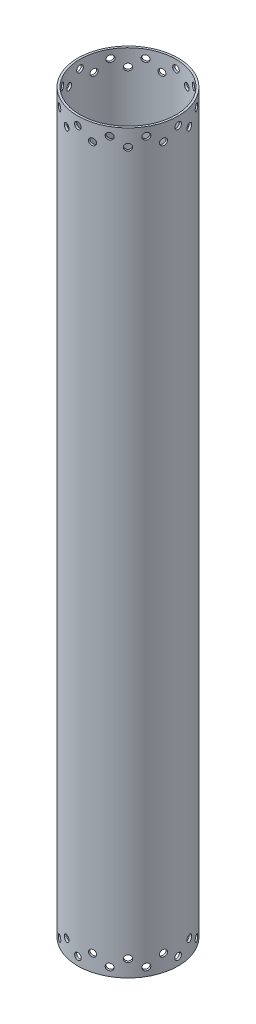
SolidWorks part; units mm, degrees
material "6061-T6 (SS)"
ref_plane "Front Plane" through (0, 0, 0) normal (0, 0, 1) x (1, 0, 0)
ref_plane "Top Plane" through (0, 0, 0) normal (0, 1, 0) x (1, 0, 0)
ref_plane "Right Plane" through (0, 0, 0) normal (1, 0, 0) x (0, 0, -1)
sketch "Sketch2" plane through (0, 0, 0) normal (0, 1, 0) x (1, 0, 0)
  circle A0 centre (0, 0) radius 76.2
  circle A1 centre (0, 0) radius 73.025
  dimension "D1" = 152.4
  dimension "D2" = 3.175
extrude "Boss-Extrude1" add sketch "Sketch2" along normal blind 1117.6
sketch "Sketch3" plane through (0, 0, 0) normal (0, 0, 1) x (1, 0, 0)
  line L0 (0, 1117.6) -> (0, 1104.9) construction
  line L1 (73.025, 1117.6) -> (-73.025, 1117.6) construction
  circle A0 centre (0, 1104.9) radius 5.0419
  dimension "D1" = 10.0838
  dimension "D2" = 12.7
extrude "Cut-Extrude1" cut sketch "Sketch3" against normal blind 1143
pattern_circular "CirPattern1" count 12 over 360 about axis through (0, 1117.6, 0) along (0, -1, 0) of "Cut-Extrude1"
ref_plane "Plane1" through (-19.722, 0, 73.6035) normal (-0.2588, 0, 0.9659) x (0, -1, 0)
sketch "Sketch6" plane through (-19.722, 0, 73.6035) normal (-0.2588, 0, 0.9659) x (0, -1, 0)
  line L0 (-1117.6, 0) -> (-1092.2, 0) construction
  line L1 (-1117.6, 76.2) -> (-1117.6, -76.2) construction
  circle A0 centre (-1092.2, 0) radius 5.0419
  dimension "D1" = 10.0838
extrude "Cut-Extrude2" cut sketch "Sketch6" against normal blind 25.4
pattern_circular "CirPattern2" count 12 over 360 about axis through (0, 1117.6, 0) along (0, -1, 0) of "Cut-Extrude2"
ref_plane "Plane2" through (0, 558.8, 0) normal (0, 1, 0) x (1, 0, 0)
mirror "Mirror1" about plane through (0, 558.8, 0) normal (0, 1, 0) of "CirPattern2", "CirPattern1"
equation "\"holeDia\"=0.397"
equation "\"D1@Sketch3\"=\"holeDia\""
equation "\"D1@Sketch6\"=\"holeDia\""
equation "\"numHoles\"=12"
equation "\"D1@CirPattern1\"=\"numHoles\""
equation "\"D1@CirPattern2\"=\"numHoles\""
equation "\"D1@Plane1\"=180/\"numHoles\""
